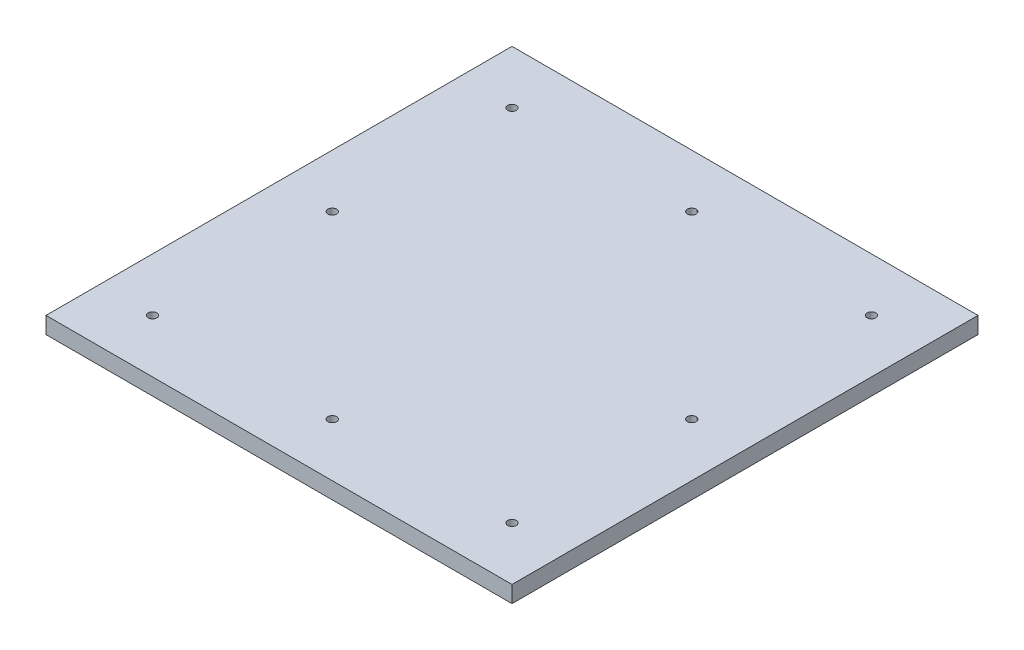
SolidWorks part; units mm, degrees
ref_plane "Front Plane" through (0, 0, 0) normal (0, 0, 1) x (1, 0, 0)
ref_plane "Top Plane" through (0, 0, 0) normal (0, 1, 0) x (1, 0, 0)
ref_plane "Right Plane" through (0, 0, 0) normal (1, 0, 0) x (0, 0, -1)
sketch "Sketch1" plane through (0, 0, 0) normal (0, 1, 0) x (1, 0, 0)
  line L1 (0, 0) -> (177.8, 0)
  line L2 (0, 0) -> (0, 177.8)
  line L3 (0, 177.8) -> (177.8, 177.8)
  line L4 (177.8, 0) -> (177.8, 177.8)
  circle A0 centre (20.32, 157.48) radius 1.6637
  circle A1 centre (88.9, 157.48) radius 1.6637
  circle A2 centre (157.48, 157.48) radius 1.6637
  circle A3 centre (20.32, 88.9) radius 1.6637
  circle A4 centre (20.32, 20.32) radius 1.6637
  circle A5 centre (88.9, 20.32) radius 1.6637
  circle A6 centre (157.48, 88.9) radius 1.6637
  circle A7 centre (157.48, 20.32) radius 1.6637
  dimension "D3" = 3.3274
  dimension "D6" = 20.32
  dimension "D12" = 20.32
  dimension "D16" = 3.3274
  dimension "D17" = 3.3274
  dimension "D18" = 3.3274
  dimension "D19" = 3.3274
  dimension "D20" = 3.3274
  dimension "D21" = 3.3274
  dimension "D22" = 3.3274
  dimension "D1" = 177.8
  dimension "D2" = 177.8
  dimension "D4" = 20.32
  dimension "D5" = 20.32
  dimension "D7" = 20.32
  dimension "D8" = 20.32
  dimension "D9" = 20.32
  dimension "D10" = 20.32
  dimension "D11" = 20.32
  dimension "D13" = 20.32
  dimension "D14" = 20.32
  dimension "D15" = 20.32
extrude "Boss-Extrude1" add sketch "Sketch1" along normal blind 6.35
